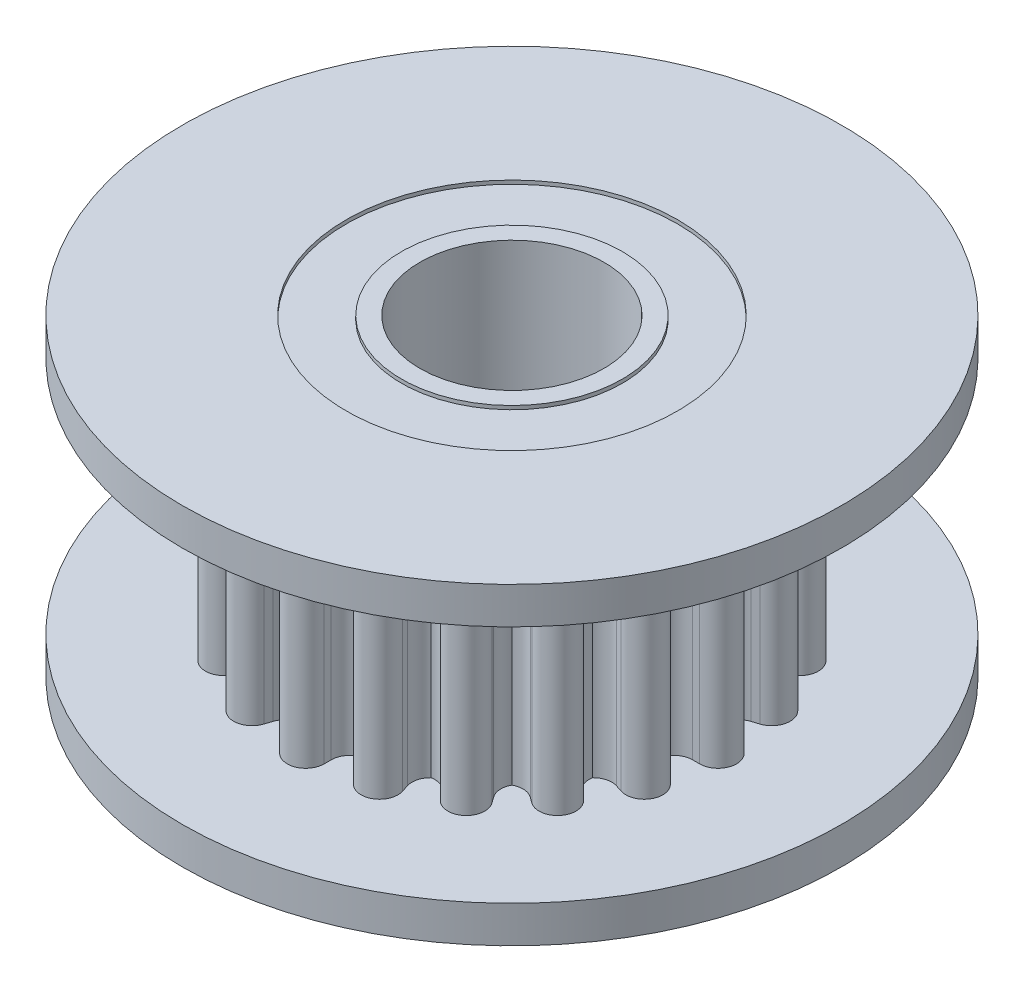
SolidWorks part; units mm, degrees
material "6063-T5"
ref_plane "Front Plane" through (0, 0, 0) normal (0, 0, 1) x (1, 0, 0)
ref_plane "Top Plane" through (0, 0, 0) normal (0, 1, 0) x (1, 0, 0)
ref_plane "Right Plane" through (0, 0, 0) normal (1, 0, 0) x (0, 0, -1)
sketch "Sketch1" plane through (0, 0, 0) normal (0, 1, 0) x (1, 0, 0)
  circle A0 centre (0, 0) radius 8.95
  circle A1 centre (0, 0) radius 2.5
  dimension "D1" = 17.9
  dimension "D2" = 5
extrude "Boss-Extrude1" add sketch "Sketch1" along normal blind 1
sketch "Sketch2" plane through (0, 1, 0) normal (0, 1, 0) x (1, 0, 0)
  circle A0 centre (0, 0) radius 5
  circle A1 centre (0, 0) radius 2.5
  dimension "D1" = 10
  dimension "D2" = 5
extrude "Boss-Extrude2" add sketch "Sketch2" along normal blind 3.25
sketch "Sketch3" plane through (0, 1, 0) normal (0, 1, 0) x (1, 0, 0)
  line L0 (-1000, 0) -> (49000, 0) construction
  line L1 (0, -1000) -> (0, 49000) construction
  line L2 (0.5, 5.6) -> (0.5, 5.4083)
  line L3 (-0.5, 5.6) -> (-0.5, 5.4083)
  line L4 (-0.9091, 4.9167) -> (0.9091, 4.9167)
  circle A0 centre (0, 0) radius 6.1 construction
  arc A3 (-0.5, 5.6) -> (0.5, 5.6) centre (0, 5.6) cw
  arc A5 (0.5, 5.4083) -> (0.9091, 4.9167) centre (1, 5.4083) ccw
  arc A6 (-0.5, 5.4083) -> (-0.9091, 4.9167) centre (-1, 5.4083) cw
  circle A9 centre (0, 0) radius 5 construction
  dimension "D1" = 12.2
  dimension "D2" = 0.5
  dimension "D3" = 0.5
  dimension "D6" = 10
ref_axis "Axis1" through (0, 4.25, 0) along (0, -1, 0)
extrude "Boss-Extrude3" add sketch "Sketch3" along normal up to surface (3.25 mm away) up to face at (0, 4.25, 5)
pattern_circular "CirPattern1" count 20 over 360 about axis through (0, 4.25, 0) along (0, -1, 0) of "Boss-Extrude3"
sketch "Sketch4" plane through (0, 0, 0) normal (0, -1, 0) x (1, 0, 0)
  circle A0 centre (0, 0) radius 4.5
  circle A1 centre (0, 0) radius 2.5
  circle A2 centre (0, 0) radius 3
  circle A3 centre (0, 0) radius 2.5 construction
  dimension "D1" = 0.5
  dimension "D2" = 9
extrude "Cut-Extrude1" cut sketch "Sketch4" against normal blind 0.1 contours A0 A2 region at (-4.3727, 0, 0)
mirror "Mirror1" about plane through (0, 4.25, 0) normal (0, 1, 0) of bodies 118 106
